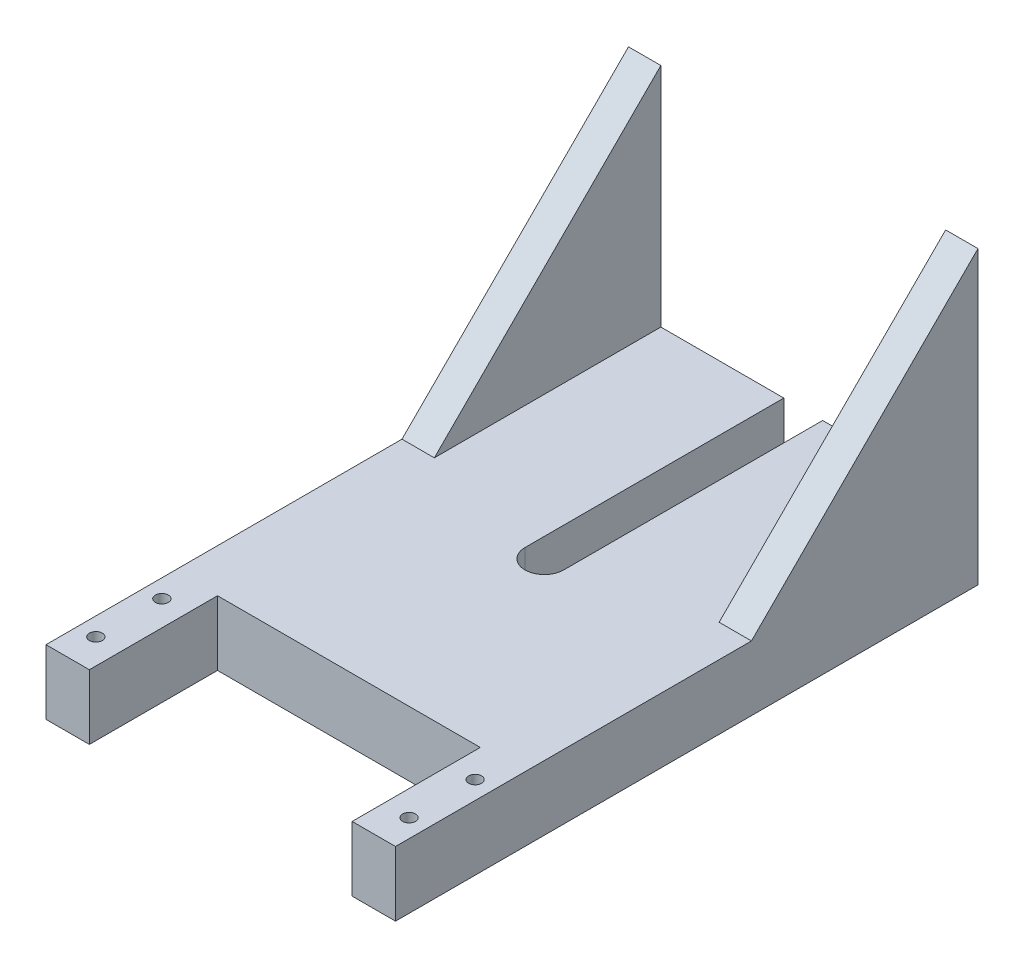
SolidWorks part; units mm, degrees
ref_plane "Front Plane" through (0, 0, 0) normal (0, 0, 1) x (1, 0, 0)
ref_plane "Top Plane" through (0, 0, 0) normal (0, 1, 0) x (1, 0, 0)
ref_plane "Right Plane" through (0, 0, 0) normal (1, 0, 0) x (0, 0, -1)
sketch "Sketch1" plane through (0, 0, 0) normal (0, 0, 1) x (1, 0, 0)
  line L0 (-16.0284, 532.1756) -> (37.9716, 532.1756)
  line L1 (-16.0284, 532.1756) -> (-16.0284, 522.1756)
  line L2 (-16.0284, 522.1756) -> (37.9716, 522.1756)
  line L3 (37.9716, 532.1756) -> (37.9716, 522.1756)
  dimension "D1" = 54
  dimension "D2" = 10
extrude "Boss-Extrude1" add sketch "Sketch1" along normal blind 90 contours L0 L3 L2 L1
sketch "Sketch2" plane through (0, 522.1756, 0) normal (0, -1, 0) x (1, 0, 0)
  line L0 (-16.0284, 90) -> (37.9716, 90) construction
  line L1 (-9.3284, 90) -> (31.2716, 90)
  line L2 (-9.3284, 90) -> (-9.3284, 70.2)
  line L3 (-9.3284, 70.2) -> (31.2716, 70.2)
  line L4 (31.2716, 90) -> (31.2716, 70.2)
  line L5 (10.9716, 70.2) -> (10.9716, 0) construction
  line L7 (-16.0284, 0) -> (37.9716, 0) construction
  dimension "D1" = 40.6
  dimension "D2" = 19.8
extrude "Cut-Extrude1" cut sketch "Sketch2" against normal through all
sketch "Sketch4" plane through (0, 532.1756, 0) normal (0, 1, 0) x (1, 0, 0)
  line L0 (10.9716, -70.2) -> (10.9716, 0) construction
  line L1 (-9.3284, -70.2) -> (31.2716, -70.2) construction
  line L2 (-16.0284, 0) -> (37.9716, 0) construction
  line L3 (10.9716, -40) -> (10.9716, 0) construction
  line L4 (7.9716, -40) -> (7.9716, 0)
  line L5 (13.9716, -40) -> (13.9716, 0)
  arc A0 (7.9716, -40) -> (13.9716, -40) centre (10.9716, -40) ccw
  arc A1 (13.9716, 0) -> (7.9716, 0) centre (10.9716, 0) ccw
  point P7 (10.9716, -20)
extrude "Cut-Extrude2" cut sketch "Sketch4" against normal through all
sketch "Sketch7" plane through (-16.0284, 0, 0) normal (-1, 0, 0) x (0, 0, 1)
  line L0 (35, 532.1756) -> (0, 567.1756)
  line L1 (90, 532.1756) -> (0, 532.1756) construction
  line L2 (0, 661.4772) -> (0, 361.4772) construction
  line L3 (0, 567.1756) -> (0, 532.1756)
  line L4 (0, 532.1756) -> (35, 532.1756)
extrude "Boss-Extrude4" add sketch "Sketch7" against normal blind 5
sketch "Sketch8" plane through (37.9716, 0, 0) normal (1, 0, 0) x (0, 0, -1)
  line L0 (-35, 532.1756) -> (0, 567.1756)
  line L1 (0, 567.1756) -> (0, 532.1756)
  line L2 (0, 532.1756) -> (-35, 532.1756)
extrude "Boss-Extrude5" add sketch "Sketch8" against normal blind 5
sketch "Sketch9" plane through (0, 522.1756, 0) normal (0, -1, 0) x (1, 0, 0)
  line L0 (-13.2284, 85.1) -> (35.1716, 85.1) construction
  line L3 (-13.2284, 74.9) -> (35.1716, 74.9) construction
  line L6 (-13.2284, 85.1) -> (-13.2284, 74.9) construction
  line L7 (35.1716, 74.9) -> (35.1716, 85.1) construction
  circle A0 centre (-13.2284, 85.1) radius 1
  circle A1 centre (-13.2284, 74.9) radius 1
  circle A2 centre (35.1716, 74.9) radius 1
  circle A3 centre (35.1716, 85.1) radius 1
extrude "Cut-Extrude3" cut sketch "Sketch9" against normal through all
